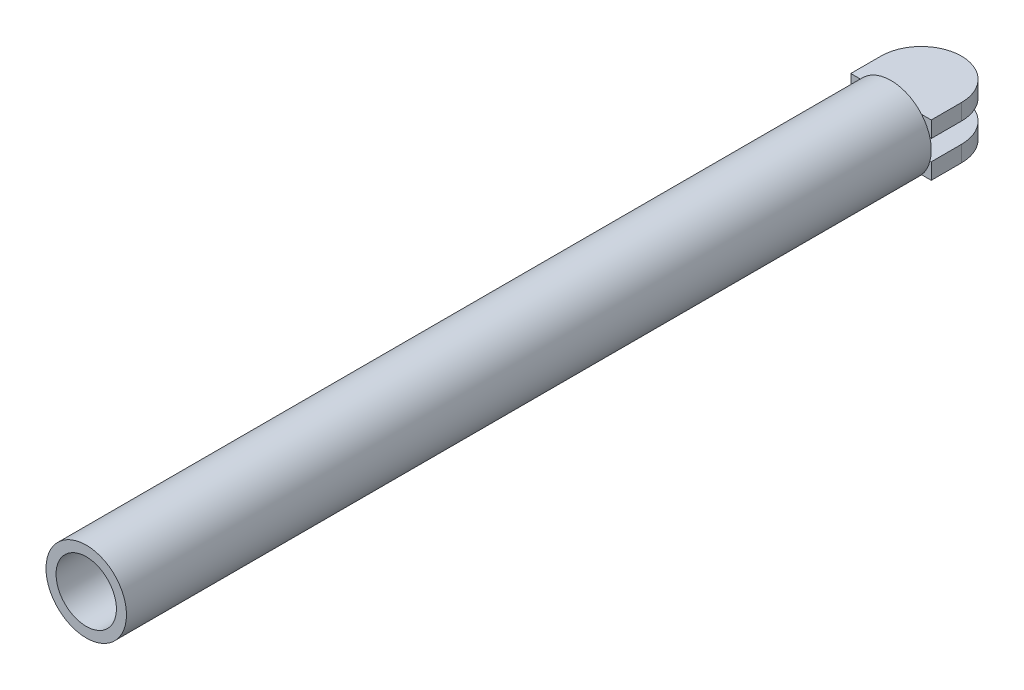
SolidWorks part; units mm, degrees
ref_plane "Front Plane" through (0, 0, 0) normal (0, 0, 1) x (1, 0, 0)
ref_plane "Top Plane" through (0, 0, 0) normal (0, 1, 0) x (1, 0, 0)
ref_plane "Right Plane" through (0, 0, 0) normal (1, 0, 0) x (0, 0, -1)
sketch "Sketch1" plane through (0, 0, 0) normal (0, 0, 1) x (1, 0, 0)
  circle A0 centre (0, 0) radius 20
  circle A1 centre (0, 0) radius 15
  dimension "D1" = 40
  dimension "D2" = 30
extrude "Boss-Extrude1" add sketch "Sketch1" along normal mid plane 400
sketch "Sketch6" plane through (0, 0, 0) normal (0, 1, 0) x (1, 0, 0)
  line L0 (20, 200) -> (-20, 200) construction
  line L1 (-20, 200) -> (20, 200)
  line L2 (-20, 200) -> (-20, 215)
  line L4 (20, 200) -> (20, 215)
  line L5 (20, -200) -> (20, 200) construction
  arc A0 (-20, 215) -> (20, 215) centre (0, 215) cw
  dimension "D1" = 15
  dimension "D2" = 40
extrude "Boss-Extrude5" add sketch "Sketch6" along normal blind 8 from offset 5
extrude "Boss-Extrude6" add sketch "Sketch6<2>" against normal blind 8 from offset 5 offset against normal yes
sketch "Sketch6<2>" plane through (0, 0, 0) normal (0, 1, 0) x (1, 0, 0) same geometry as "Sketch6"
sketch "Sketch7" plane through (0, -13, 0) normal (0, -1, 0) x (1, 0, 0)
  circle A0 centre (0, -215) radius 3.5
  dimension "D1" = 7
extrude "Boss-Extrude7" add sketch "Sketch7" against normal blind 10 from offset 8 offset against normal yes
